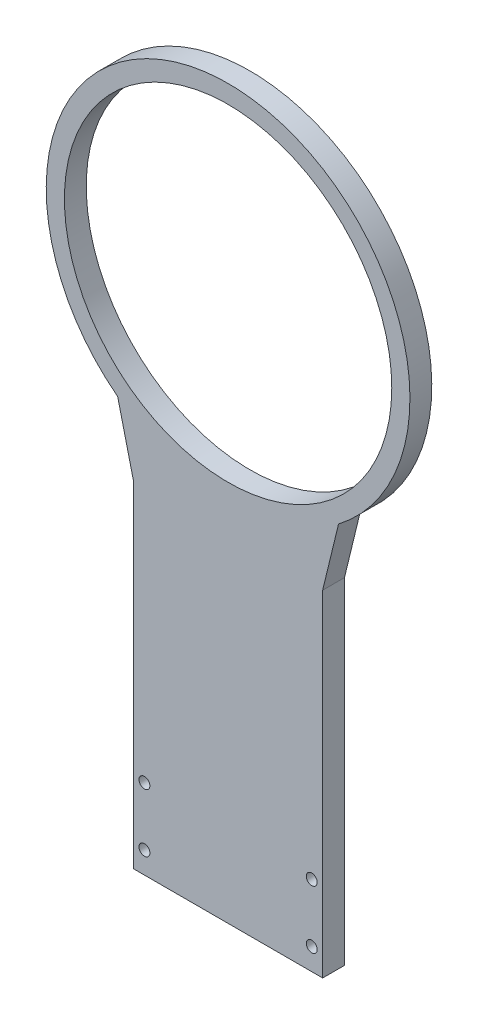
SolidWorks part; units mm, degrees
ref_plane "Front" through (0, 0, 0) normal (0, 0, 1) x (1, 0, 0)
ref_plane "Top" through (0, 0, 0) normal (0, 1, 0) x (1, 0, 0)
ref_plane "Right" through (0, 0, 0) normal (1, 0, 0) x (0, 0, -1)
sketch "Esquisse1" plane through (0, 0, 0) normal (0, 0, 1) x (1, 0, 0)
  line L1 (0, 0) -> (100, 0)
  line L2 (0, 0) -> (0, 100)
  line L3 (0, 100) -> (100, 100)
  line L4 (100, 0) -> (100, 100)
  dimension "D1" = 100
  dimension "D2" = 100
extrude "Boss.-Extru.1" add sketch "Esquisse1" along normal blind 6
sketch "Esquisse2" plane through (0, 0, 6) normal (0, 0, 1) x (1, 0, 0)
  line L1 (50, 0) -> (50, 100) construction
  line L2 (0, 0) -> (100, 0) construction
  line L3 (100, 100) -> (0, 100) construction
  circle A0 centre (50, 50) radius 45
  dimension "D1" = 90
extrude "Enlèv. mat.-Extru.1" cut sketch "Esquisse2" against normal through all
sketch "Esquisse3" plane through (0, 0, 6) normal (0, 0, 1) x (1, 0, 0)
  line L0 (100, 0) -> (100, 100) construction
  line L1 (0, 0) -> (100, 0)
  line L2 (0, 0) -> (0, -100)
  line L3 (0, -100) -> (100, -100)
  line L4 (100, 0) -> (100, -100)
  dimension "D1" = 100
extrude "Boss.-Extru.2" add sketch "Esquisse3" against normal up to vertex (6 mm away) up to point (100, 0, 0)
sketch "Esquisse4" plane through (0, 0, 6) normal (0, 0, 1) x (1, 0, 0)
  line L0 (50, -100) -> (50, -3.3563) construction
  line L1 (0, -100) -> (100, -100) construction
  line L2 (0, 100) -> (0, -100) construction
  line L3 (24, -100) -> (0, -100)
  line L4 (24, -100) -> (24, 0)
  line L5 (24, 0) -> (0, 0)
  line L6 (0, -100) -> (0, 0)
  line L7 (100, -100) -> (100, 0)
  line L8 (76, 0) -> (100, 0)
  line L9 (76, -100) -> (76, 0)
  line L10 (76, -100) -> (100, -100)
  dimension "D1" = 52
  dimension "D2" = 100
extrude "Enlèv. mat.-Extru.2" cut sketch "Esquisse4" against normal up to vertex (106 mm away) up to point (0, 100, -100)
sketch "Esquisse5" plane through (0, 0, 6) normal (0, 0, 1) x (1, 0, 0)
  line L0 (50, -100) -> (50, -10.2588) construction
  line L1 (24, -100) -> (76, -100) construction
  line L2 (27, -100) -> (27, -78) construction
  line L3 (24, -100) -> (24, 0) construction
  circle A0 centre (27, -78) radius 1.5
  circle A1 centre (27, -94) radius 1.5
  circle A2 centre (73, -94) radius 1.5
  circle A3 centre (73, -78) radius 1.5
  dimension "D1" = 16
  dimension "D2" = 6
  dimension "D4" = 3
  dimension "D3" = 3
extrude "Enlèv. mat.-Extru.3" cut sketch "Esquisse5" against normal through all
sketch "Esquisse6" plane through (0, 0, 6) normal (0, 0, 1) x (1, 0, 0)
  line L0 (76, 7.2917) -> (76, 0)
  line L1 (24, 0) -> (24, 7.2917)
  line L2 (100, 0) -> (100, 100) construction
  line L3 (24, 0) -> (-1, 0)
  line L4 (-1, 0) -> (-1, 101)
  line L5 (50, 50) -> (50, 80.2211) construction
  line L6 (50, 80.2211) -> (50, 101) construction
  line L7 (-1, 101) -> (101, 101)
  line L8 (100, 100) -> (0, 100) construction
  line L9 (0, 100) -> (0, 0) construction
  line L10 (76, 0) -> (101, 0)
  line L11 (101, 0) -> (101, 101)
  arc A0 (24, 7.2917) -> (76, 7.2917) centre (50, 50) cw
  dimension "D1" = 1
  dimension "D2" = 1
extrude "Enlèv. mat.-Extru.4" cut sketch "Esquisse6" against normal through all
chamfer "Chanfrein1" distance 5 angle 45 2 edges at (24, 7.2917, 3) (76, 7.2917, 3) first distance on face at (50, 53.6458, 3)
